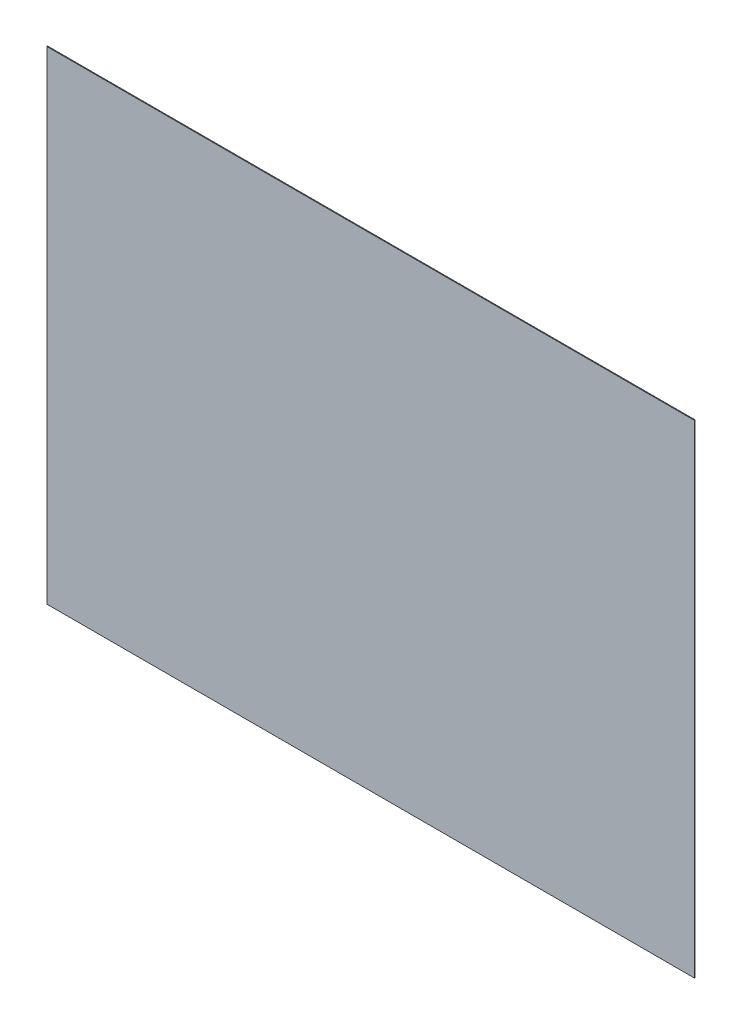
SolidWorks part; units mm, degrees
ref_plane "Front Plane" through (0, 0, 0) normal (0, 0, 1) x (1, 0, 0)
ref_plane "Top Plane" through (0, 0, 0) normal (0, 1, 0) x (1, 0, 0)
ref_plane "Right Plane" through (0, 0, 0) normal (1, 0, 0) x (0, 0, -1)
other "Configuration Table"
sketch "Sketch2" plane through (0, 0, 0) normal (0, 0, 1) x (1, 0, 0)
  line L1 (0, 0) -> (12000, 0)
  line L2 (0, 0) -> (0, 8950)
  line L3 (0, 8950) -> (12000, 8950)
  line L4 (12000, 0) -> (12000, 8950)
  dimension "D1" = 8950
  dimension "D2" = 12000
sheet metal parameters "Sheet-Metal1" thickness 15 parameters "D1"=0.7366
base flange "Base-Flange1" sketch "Sketch2" thickness 15 reverse thickness direction yes parameters "D1"=0.7366
flat pattern "Flat-Pattern1" [suppressed]
sketch "Bend-Lines1" plane through (0, 0, 0) normal (0, 1, 0) x (-1, 0, 0)
